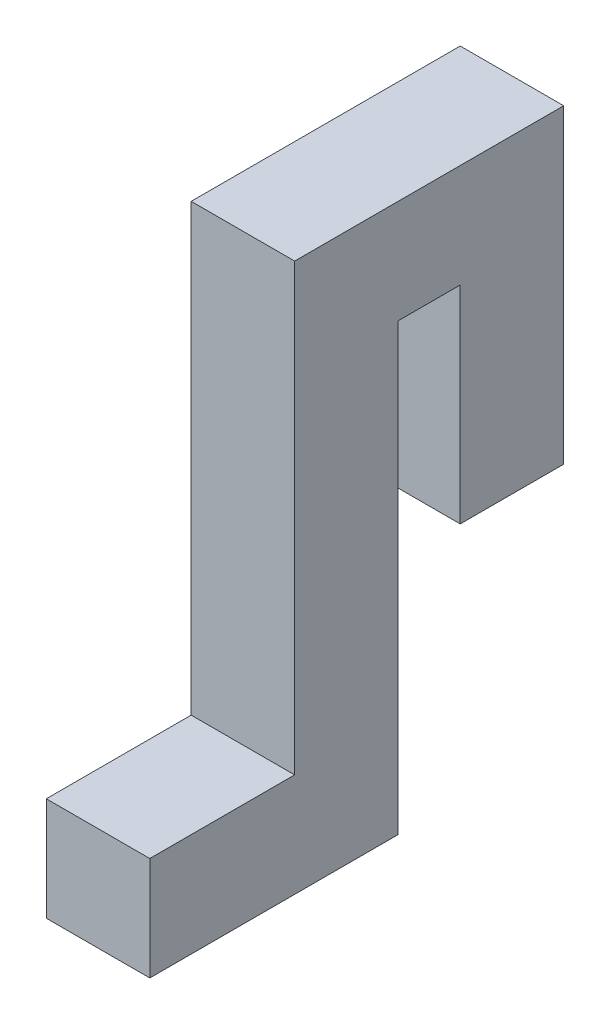
SolidWorks part; units mm, degrees
ref_plane "Front Plane" through (0, 0, 0) normal (0, 0, 1) x (1, 0, 0)
ref_plane "Top Plane" through (0, 0, 0) normal (0, 1, 0) x (1, 0, 0)
ref_plane "Right Plane" through (0, 0, 0) normal (1, 0, 0) x (0, 0, -1)
sketch "Sketch1" plane through (0, 0, 0) normal (1, 0, 0) x (0, 0, -1)
  line L0 (-63.5, 273.05) -> (63.5, -273.05) construction
  line L1 (-241.3, -273.05) -> (-63.5, -273.05)
  line L2 (-241.3, -273.05) -> (-241.3, -400.05)
  line L3 (-241.3, -400.05) -> (63.5, -400.05)
  line L4 (63.5, -273.05) -> (63.5, -400.05)
  line L5 (63.5, 273.05) -> (63.5, 146.05) construction
  line L6 (63.5, -273.05) -> (63.5, 146.05)
  line L7 (63.5, 273.05) -> (-63.5, 273.05)
  line L8 (-63.5, -273.05) -> (-63.5, 273.05)
  line L9 (63.5, 273.05) -> (266.7, 273.05)
  line L10 (-63.5, -273.05) -> (63.5, -273.05) construction
  line L11 (63.5, 146.05) -> (139.7, 146.05)
  line L12 (266.7, 273.05) -> (266.7, 146.05)
  line L13 (139.7, 146.05) -> (266.7, 146.05) construction
  line L14 (266.7, 146.05) -> (266.7, -107.95)
  line L15 (266.7, -107.95) -> (139.7, -107.95)
  line L16 (139.7, 146.05) -> (139.7, -107.95)
  dimension "D1" = 304.8
  dimension "D2" = 127
  dimension "D3" = 546.1
  dimension "D4" = 127
  dimension "D5" = 203.2
  dimension "D6" = 127
  dimension "D7" = 254
  dimension "D8" = 127
extrude "Boss-Extrude1" add sketch "Sketch1" along normal mid plane 127
